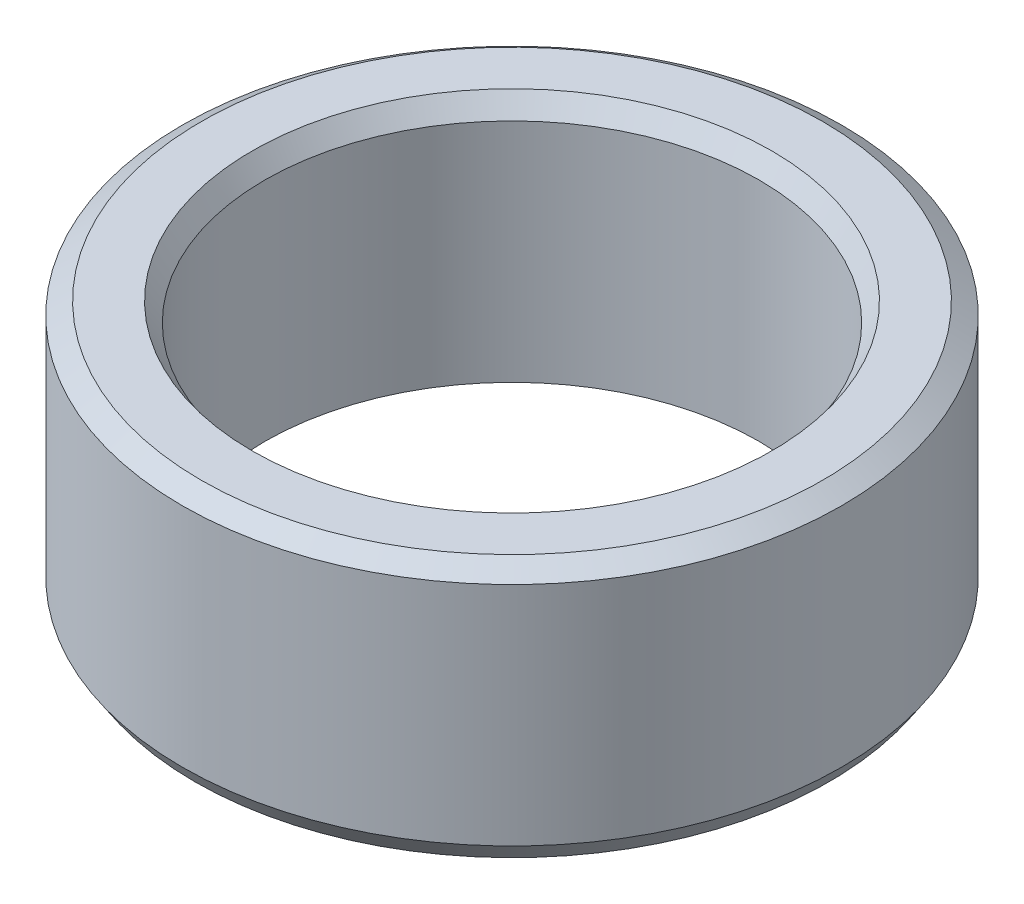
SolidWorks part; units mm, degrees
ref_plane "Front Plane" through (0, 0, 0) normal (0, 0, 1) x (1, 0, 0)
ref_plane "Top Plane" through (0, 0, 0) normal (0, 1, 0) x (1, 0, 0)
ref_plane "Right Plane" through (0, 0, 0) normal (1, 0, 0) x (0, 0, -1)
sketch "Sketch1" plane through (0, 0, 0) normal (0, 1, 0) x (1, 0, 0)
  circle A0 centre (0, 0) radius 45
  dimension "SLEEVE_OD" = 90
extrude "Boss-Extrude1" add sketch "Sketch1" along normal blind 35.2061
sketch "Sketch2" plane through (0, 0, 0) normal (0, 1, 0) x (1, 0, 0)
  circle A0 centre (0, 0) radius 33.7513
  dimension "BORE_D" = 67.5026
extrude "Cut-Extrude1" cut sketch "Sketch2" along normal through all
chamfer "Chamfer1" distance 1.714 angle 56.506 4 edges at (0, 35.2061, 33.7513) (0, 0, 33.7513) (0, 0, 45) (0, 35.2061, 45) first distance on face at (0, 35.2061, 33.7513) first distance on face at (0, 0, 33.7513) first distance on face at (0, 35.2061, 45)
